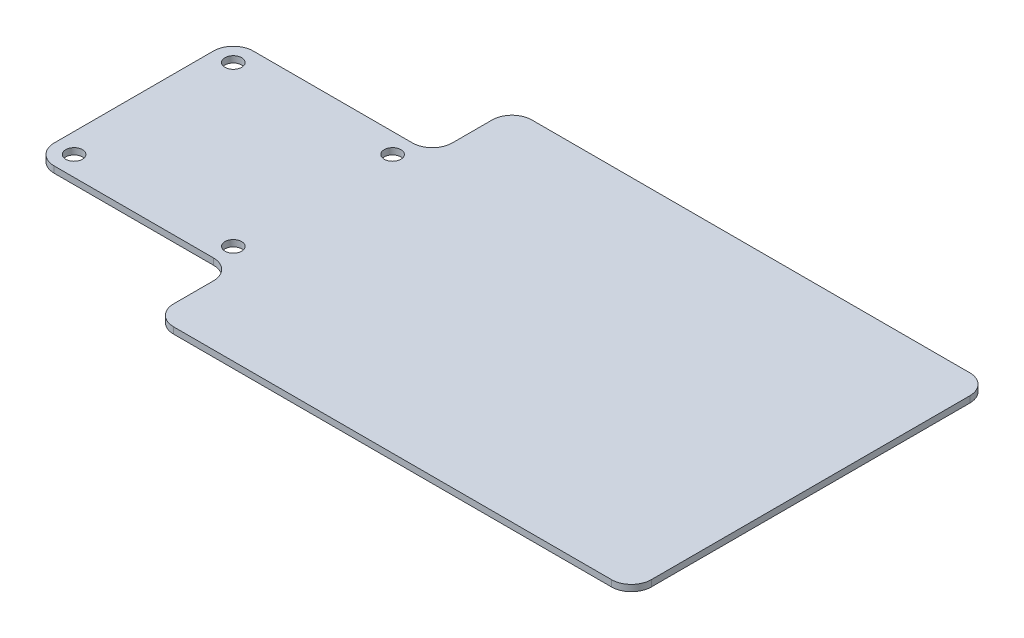
SolidWorks part; units mm, degrees
ref_plane "Front Plane" through (0, 0, 0) normal (0, 0, 1) x (1, 0, 0)
ref_plane "Top Plane" through (0, 0, 0) normal (0, 1, 0) x (1, 0, 0)
ref_plane "Right Plane" through (0, 0, 0) normal (1, 0, 0) x (0, 0, -1)
sketch "Sketch1" plane through (0, 0, 0) normal (0, 1, 0) x (1, 0, 0)
  line L0 (-25, 25) -> (25, 25)
  line L1 (25, 45) -> (145, 45)
  line L2 (-25, 25) -> (-25, -25)
  line L3 (25, -45) -> (145, -45)
  line L4 (145, 45) -> (145, -45)
  line L5 (25, 25) -> (25, 45)
  line L6 (-25, -25) -> (25, -25)
  line L7 (25, -25) -> (25, -45)
  dimension "D1" = 120
  dimension "D2" = 25
  dimension "D3" = 25
  dimension "D4" = 90
  dimension "D5" = 50
  dimension "D6" = 20
  dimension "D7" = 50
extrude "Boss-Extrude1" add sketch "Sketch1" along normal blind 1.6
fillet "Fillet1" radius 5 8 edges at (145, 0.8, -45) (145, 0.8, 45) (25, 0.8, -45) (25, 0.8, -25) (-25, 0.8, -25) (-25, 0.8, 25) (25, 0.8, 25) (25, 0.8, 45)
sketch "Sketch2" plane through (0, 1.6, 0) normal (0, 1, 0) x (1, 0, 0)
  line L0 (0, 20) -> (0, -20) construction
  line L1 (-20, 20) -> (20, 20) construction
  line L2 (-20, 20) -> (-20, -20) construction
  line L3 (-20, -20) -> (20, -20) construction
  line L4 (20, 20) -> (20, -20) construction
  circle A0 centre (-20, 20) radius 2.1
  circle A1 centre (20, 20) radius 2.1
  circle A2 centre (20, -20) radius 2.1
  circle A3 centre (-20, -20) radius 2.1
  dimension "D1" = 4.2
  dimension "D2" = 40
  dimension "D3" = 40
extrude "Cut-Extrude1" cut sketch "Sketch2" against normal through all
